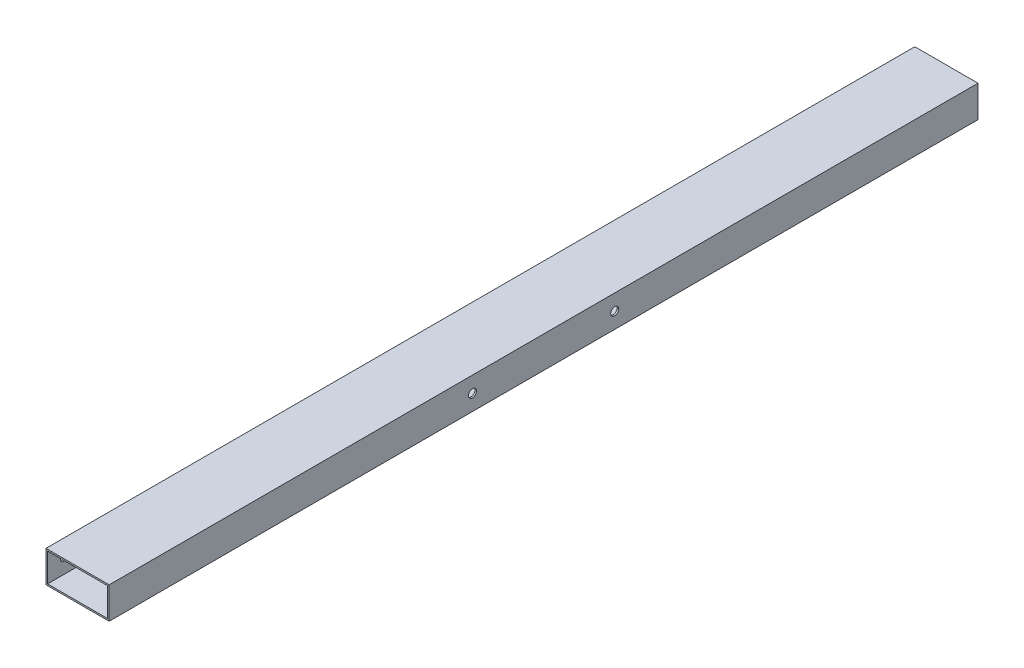
SolidWorks part; units mm, degrees
material "1060 合金"
ref_plane "前视基准面" through (0, 0, 0) normal (0, 0, 1) x (1, 0, 0)
ref_plane "上视基准面" through (0, 0, 0) normal (0, 1, 0) x (1, 0, 0)
ref_plane "右视基准面" through (0, 0, 0) normal (1, 0, 0) x (0, 0, -1)
other "Configuration Table"
sketch "草图1" plane through (0, 0, 0) normal (0, 0, 1) x (1, 0, 0)
  line L1 (0, 0) -> (40, 0)
  line L2 (0, 0) -> (0, -20)
  line L3 (0, -20) -> (40, -20)
  line L4 (40, 0) -> (40, -20)
  dimension "D1" = 20
  dimension "D2" = 40
extrude "拉伸-薄壁1" add sketch "草图1" along normal blind 550 thin thin type one direction reverse wall 1
sketch "草图4" plane through (0, 0, 0) normal (-1, 0, 0) x (0, 0, 1)
  line L0 (550, 0) -> (0, 0) construction
  line L1 (550, 0) -> (550, -20) construction
  line L4 (0, -180.2783) -> (0, 689.7217) construction
  circle A1 centre (539.9964, -10) radius 1.75
  circle A49 centre (10, -10) radius 1.75
  dimension "D27" = 3.5
  dimension "D28" = 3.5
  dimension "D29" = 10
  dimension "D25" = 10
  dimension "D26" = 10.0036
  dimension "D30" = 10
extrude "切除-拉伸2" cut sketch "草图4" against normal blind 1.5
sketch "草图5" plane through (0, 0, 0) normal (-1, 0, 0) x (0, 0, 1)
  circle A0 centre (42.5, -10) radius 1.75 construction
  circle A1 centre (42.5, -10) radius 1.75
  circle A2 centre (62.5, -10) radius 1.75
  circle A3 centre (82.5, -10) radius 1.75
  circle A4 centre (102.5, -10) radius 1.75
  circle A5 centre (122.5, -10) radius 1.75
  circle A6 centre (142.5, -10) radius 1.75
  circle A7 centre (162.5, -10) radius 1.75
  circle A8 centre (182.5, -10) radius 1.75
  circle A9 centre (202.5, -10) radius 1.75
  circle A10 centre (222.5, -10) radius 1.75
  circle A11 centre (242.5, -10) radius 1.75
  circle A12 centre (262.5, -10) radius 1.75
  circle A13 centre (282.5, -10) radius 1.75
  circle A14 centre (302.5, -10) radius 1.75
  circle A15 centre (322.5, -10) radius 1.75
  circle A16 centre (342.5, -10) radius 1.75
  circle A17 centre (362.5, -10) radius 1.75
  circle A18 centre (382.5, -10) radius 1.75
  circle A19 centre (402.5, -10) radius 1.75
  circle A20 centre (422.5, -10) radius 1.75
  circle A21 centre (442.5, -10) radius 1.75
  circle A22 centre (462.5, -10) radius 1.75
  circle A23 centre (482.5, -10) radius 1.75
  dimension "D1" = 23
sketch "草图6" plane through (40, 0, 0) normal (1, 0, 0) x (0, 0, -1)
  line L0 (-550, -20) -> (0, -20) construction
  line L1 (-550, -20) -> (-550, 0) construction
  circle A0 centre (-320, -10) radius 2.5
  circle A1 centre (-230, -10) radius 2.5
  dimension "D1" = 5
  dimension "D2" = 5
  dimension "D3" = 10
  dimension "D4" = 10
  dimension "D5" = 230
  dimension "D6" = 230
extrude "切除-拉伸3" cut sketch "草图6" against normal through all
